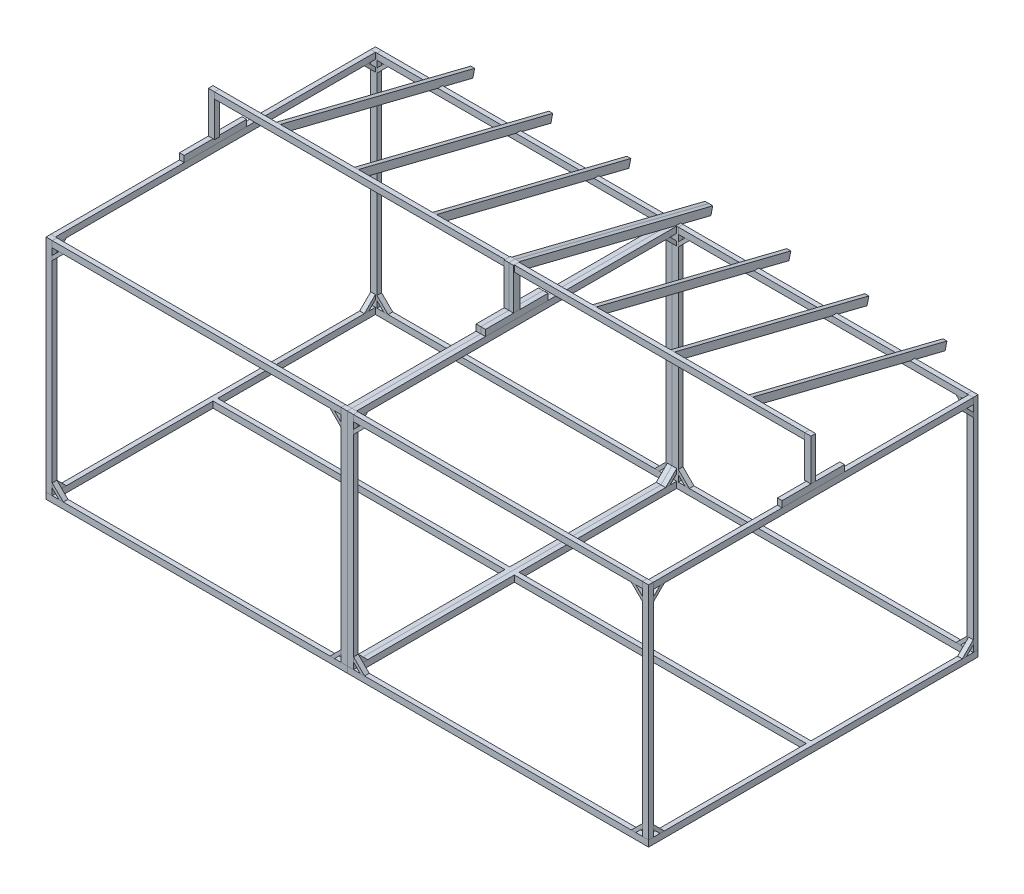
SolidWorks part; units mm, degrees
ref_plane "Front Plane" through (0, 0, 0) normal (0, 0, 1) x (1, 0, 0)
ref_plane "Top Plane" through (0, 0, 0) normal (0, 1, 0) x (1, 0, 0)
ref_plane "Right Plane" through (0, 0, 0) normal (1, 0, 0) x (0, 0, -1)
other "Configuration Table"
sketch "MetalBase" plane through (0, 0, 0) normal (0, 1, 0) x (1, 0, 0)
  line L0 (-60, -60) -> (7660, -60)
  line L1 (0, 0) -> (7600, 0)
  line L2 (0, 0) -> (0, 2020)
  line L3 (0, 4100) -> (7600, 4100)
  line L4 (7600, 0) -> (7600, 2020)
  line L5 (7660, -60) -> (7660, 4160)
  line L6 (-60, 4160) -> (7660, 4160)
  line L7 (-60, -60) -> (-60, 4160)
  line L8 (0, 2050) -> (7600, 2050) construction
  line L9 (0, 2020) -> (7600, 2020)
  line L10 (0, 2080) -> (7600, 2080)
  line L11 (0, 2080) -> (0, 4100)
  line L12 (7600, 2080) -> (7600, 4100)
  line L13 (0, 0) -> (0, 4100) construction
  line L15 (7600, 0) -> (7600, 4100) construction
  point P15 (7660, 2050)
  dimension "D1" = 4100
  dimension "D2" = 7600
  dimension "D6" = 4220
  dimension "D7" = 7720
  dimension "D3" = 60
  dimension "D4" = 30
  dimension "D5" = 30
sketch "InternalSpace" plane through (0, 0, 0) normal (0, 1, 0) x (1, 0, 0)
  line L26 (50, 50) -> (7550, 50)
  line L27 (7550, 50) -> (7550, 4050)
  line L28 (7550, 4050) -> (50, 4050)
  line L29 (50, 4050) -> (50, 50)
  line L30 (50, 50) -> (7550, 50)
  line L31 (7550, 50) -> (7550, 4050)
  line L32 (7550, 4050) -> (50, 4050)
  line L33 (50, 4050) -> (50, 50)
  dimension "D2" = 4000
  dimension "D3" = 7500
  dimension "D1" = 110
sketch "Furniture" plane through (0, 0, 0) normal (0, 1, 0) x (1, 0, 0)
  line L0 (6750, 2050) -> (6750, 4050)
  line L1 (2200, 2550) -> (1400, 2550)
  line L2 (2200, 2550) -> (2200, 4050)
  line L3 (2200, 4050) -> (1400, 4050)
  line L4 (1400, 2550) -> (1400, 4050)
  line L5 (1050, 50) -> (50, 50)
  line L6 (1050, 50) -> (1050, 2050)
  line L7 (1050, 2050) -> (50, 2050)
  line L8 (50, 50) -> (50, 2050)
  line L9 (6350, 2110) -> (7550, 2110)
  line L10 (2200, 4050) -> (2200, 150)
  line L11 (0, 0) -> (7600, 0) construction
  line L12 (6350, 50) -> (6350, 2110)
  line L13 (6470, 50) -> (6470, 1990)
  line L15 (2200, 2050) -> (7550, 2050) construction
  line L17 (1979.5569, 919.0285) -> (2200, 150)
  line L18 (6350, 150) -> (5722.0427, 459.305)
  line L19 (6710, 1120.0467) -> (7310, 1120.0467)
  line L24 (6710, 1120.0467) -> (6710, 1880.0467)
  line L25 (6710, 1880.0467) -> (7310, 1880.0467)
  line L26 (7310, 1120.0467) -> (7310, 1880.0467)
  line L27 (6350, 2110) -> (5750, 2110)
  line L28 (6350, 2110) -> (6350, 1510)
  line L29 (6350, 1510) -> (5750, 1510)
  line L30 (5750, 2110) -> (5750, 1510)
  line L31 (2320, 2050) -> (4320, 2050) construction
  line L32 (4320, 2050) -> (4320, 4050) construction
  line L33 (2200, 150) -> (2499.3532, 150) construction
  line L34 (2499.3532, 150) -> (2499.3532, 981.1813) construction
  line L35 (2499.3532, 981.1813) -> (2200, 981.1813) construction
  line L36 (2320, 4050) -> (2320, 150)
  line L37 (2200, 150) -> (2200, 50)
  line L38 (50, 50) -> (7550, 50) construction
  line L39 (2320, 150) -> (2320, 50)
  line L40 (7550, 4050) -> (50, 4050) construction
  line L41 (7550, 50) -> (7550, 4050) construction
  line L42 (50, 4050) -> (50, 50) construction
  line L43 (7550, 4050) -> (50, 4050) construction
  line L44 (7550, 50) -> (7550, 4050) construction
  line L45 (50, 50) -> (7550, 50) construction
  line L46 (50, 4050) -> (50, 50) construction
  line L47 (7010, 1120.0467) -> (7010, 1445.9123) construction
  line L48 (6470, 1990) -> (7550, 1990)
  line L49 (-60, -60) -> (-60, 4160) construction
  line L50 (7550, 809.8905) -> (7383.7397, 809.8905)
  line L51 (7550, 809.8905) -> (7550, 230.8186)
  line L52 (7550, 230.8186) -> (7383.7397, 230.8186)
  line L53 (7283.7397, 709.8905) -> (7283.7397, 330.8186)
  line L54 (7660, 4160) -> (-60, 4160) construction
  line L55 (-60, 4160) -> (-60, -60) construction
  line L56 (-60, -60) -> (7660, -60) construction
  line L57 (7660, -60) -> (7660, 4160) construction
  arc A1 (1979.5569, 919.0285) -> (1414.1883, 0) centre (2200, 150) ccw construction
  arc A2 (5722.0427, 459.305) -> (6350, 850) centre (6350, 150) cw construction
  arc A3 (7383.7397, 230.8186) -> (7283.7397, 330.8186) centre (7383.7397, 330.8186) cw
  arc A4 (7383.7397, 809.8905) -> (7283.7397, 709.8905) centre (7383.7397, 709.8905) ccw
  point P56 (7010, 1990)
  dimension "D13" = 600
  dimension "D21" = 100
  dimension "D1" = 1500
  dimension "D2" = 800
  dimension "D3" = 2000
  dimension "D4" = 1000
  dimension "D5" = 100
  dimension "D6" = 60
  dimension "D7" = 700
  dimension "D8" = 600
  dimension "D9" = 2260
  dimension "D10" = 800
  dimension "D11" = 100
  dimension "D12" = 760
  dimension "D14" = 2000
  dimension "D15" = 800
  dimension "D16" = 2000
  dimension "D17" = 600
  dimension "D18" = 60
  dimension "D19" = 4150
  dimension "D20" = 120
  dimension "D22" = 120
  dimension "D23" = 110
  dimension "D25" = 4220
  dimension "D26" = 1200
  dimension "D27" = 4030
  dimension "D24" = 110
sketch "Metal frame" plane through (0, 0, 0) normal (0, 1, 0) x (1, 0, 0)
  line L0 (0, 4100) -> (7600, 4100) construction
  line L1 (0, 4100) -> (7600, 4100)
  line L3 (0, 0) -> (0, 2020)
  line L4 (0, 0) -> (7600, 0) construction
  line L5 (0, 0) -> (7600, 0)
  line L7 (7600, 0) -> (7600, 2020)
  line L8 (-60, 4160) -> (7660, 4160)
  line L9 (7660, -60) -> (7660, 4160)
  line L10 (-60, -60) -> (7660, -60)
  line L11 (-60, -60) -> (-60, 4160)
  line L12 (0, 2050) -> (62.1159, 2050) construction
  line L13 (7600, 2080) -> (0, 2080)
  line L15 (7600, 2020) -> (0, 2020)
  line L17 (7600, 2080) -> (7600, 4100)
  line L18 (0, 2080) -> (0, 4100)
  line L19 (7600, 0) -> (7600, 4100) construction
  line L21 (0, 0) -> (0, 4100) construction
  point P14 (-60, 2050)
  dimension "D2" = 7720
  dimension "D3" = 4220
  dimension "D4" = 60
  dimension "D1" = 60
sketch "Walls bottom" plane through (0, 0, 0) normal (0, 1, 0) x (1, 0, 0)
  line L0 (-60, 4160) -> (7660, 4160) construction
  line L2 (-60, -60) -> (7660, -60) construction
  line L3 (7660, -60) -> (7660, 4160) construction
  line L4 (-60, -60) -> (-60, 4160) construction
  line L5 (-60, -60) -> (7660, -60)
  line L6 (7660, -60) -> (7660, 4160)
  line L7 (-60, 4160) -> (7660, 4160)
  line L8 (-60, -60) -> (-60, 4160)
  line L9 (40, 40) -> (40, 4060)
  line L10 (40, 4060) -> (7560, 4060)
  line L11 (7560, 40) -> (7560, 4060)
  line L12 (40, 40) -> (7560, 40)
  dimension "D2" = 4020
  dimension "D3" = 7520
  dimension "D4" = 7720
  dimension "D5" = 4220
  dimension "D1" = 100
sketch "Sketch15" plane through (0, 0, 0) normal (0, 1, 0) x (1, 0, 0)
  line L2 (7550, 50) -> (5502.4266, 50)
  line L3 (7550, 50) -> (7550, 1250)
  line L4 (7550, 1250) -> (5502.4266, 1250)
  line L5 (5502.4266, 50) -> (5502.4266, 1250)
  dimension "D1" = 1200
extrude "MetalFrame" add sketch "Metal frame" against normal blind 80 contours L11 L10 L9 L8 L15 L7 L5 L3 L13 L18 L1 L17 region at (3800, 0, -2050)
sketch "Sketch18" plane through (0, 0, 0) normal (0, 1, 0) x (1, 0, 0)
  line L0 (0, 0) -> (7600, 0) construction
  line L1 (3800, -1014.8769) -> (8467.9433, -1014.8769)
  line L2 (3800, -1014.8769) -> (3800, 5493.3133)
  line L3 (3800, 5493.3133) -> (8467.9433, 5493.3133)
  line L4 (8467.9433, -1014.8769) -> (8467.9433, 5493.3133)
  point P6 (3800, 0)
extrude "Cut-Extrude1" cut sketch "Sketch18" against normal through all
sketch "Sketch19" plane through (0, 0, 0) normal (0, 1, 0) x (1, 0, 0)
  line L0 (0, 0) -> (3800, 0) construction
  line L1 (3800, 4100) -> (3740, 4100)
  line L2 (3800, 4100) -> (3800, 0)
  line L3 (3800, 0) -> (3740, 0)
  line L4 (3740, 4100) -> (3740, 0)
  dimension "D1" = 60
extrude "Boss-Extrude1" add sketch "Sketch19" against normal blind 80
sketch "Roof" plane through (0, 0, 0) normal (1, 0, 0) x (0, 0, -1)
  line L0 (2050, 0) -> (2050, 3357.5) construction
  line L1 (4160, 0) -> (-60, 0) construction
  line L2 (4160, 0) -> (4160, 2830) construction
  line L3 (4160, 2830) -> (2050, 3357.5) construction
  line L4 (2050, 3357.5) -> (5424.8088, 3357.5) construction
  line L5 (4160, 2830) -> (4548.057, 2732.9857) construction
  line L6 (4160, 150) -> (-211.81, 150) construction
  line L7 (4160, 2830) -> (2960, 2830)
  line L8 (2960, 2830) -> (2960, 3130)
  line L9 (4160, 2750) -> (2401.0379, 2750) construction
  dimension "D2" = 1200
  dimension "D3" = 150
  dimension "D4" = 2174.9382
  dimension "D5" = 400
  dimension "D6" = 2574.9382
  dimension "D7" = 2830
  dimension "D8" = 300
  dimension "D9" = 3207.5
  dimension "D10" = 14.036
  dimension "D11" = 80
  dimension "D12" = 2600
sketch "Sketch23" plane through (-60, 0, 0) normal (1, 0, 0) x (0, 0, -1)
  line L0 (2050, 0) -> (2050, 3357.5) construction
  line L1 (4160, 0) -> (4100, 0)
  line L2 (4160, 0) -> (4160, 2830)
  line L3 (4160, 2830) -> (4100, 2830)
  line L4 (4100, 0) -> (4100, 2830)
  line L5 (0, 0) -> (0, 2830)
  line L6 (-60, 2830) -> (0, 2830)
  line L7 (-60, 0) -> (-60, 2830)
  line L8 (-60, 0) -> (0, 0)
  line L10 (0, 2830) -> (4100, 2830)
  line L11 (0, 2830) -> (0, 2750)
  line L12 (0, 2750) -> (4100, 2750)
  line L13 (4100, 2830) -> (4100, 2750)
  line M8 (-60, 0) -> (4160, 0)
  dimension "D1" = 60
  dimension "D2" = 80
extrude "Boss-Extrude5" add sketch "Sketch23" along normal blind 80 separate body contours L4 L3 L2 M8 | L7 L6 L5 M8 region at (-60, 1415, -4130) region at (-60, 1415, 30)
extrude "Boss-Extrude6" add sketch "Sketch23<3>" along normal blind 60 separate body contours L0 L12 L5 L10 | L12 L0 L10 L4 region at (-60, 2790, -1025) region at (-60, 2790, -3075)
sketch "Sketch23<3>" plane through (-60, 0, 0) normal (1, 0, 0) x (0, 0, -1) same geometry as "Sketch23"
extrude "Boss-Extrude7" add sketch "Sketch23<5>" against normal blind 80 from surface separate body contours L4 L3 L2 M8 | L7 L6 L5 M8 region at (-60, 1415, -4130) region at (-60, 1415, 30) starting at face at (3800, -40, -2050)
sketch "Sketch23<5>" plane through (-60, 0, 0) normal (1, 0, 0) x (0, 0, -1) same geometry as "Sketch23"
extrude "Boss-Extrude8" add sketch "Sketch23<6>" against normal blind 60 from surface separate body contours L12 L0 L10 L4 | L0 L12 L5 L10 region at (-60, 2790, -1025) region at (-60, 2790, -3075) starting at face at (3800, 1415, 30)
sketch "Sketch23<6>" plane through (-60, 0, 0) normal (1, 0, 0) x (0, 0, -1) same geometry as "Sketch23"
sketch "Sketch24" plane through (0, 2830, 0) normal (0, 1, 0) x (1, 0, 0)
  line L1 (20, 4160) -> (3720, 4160)
  line L2 (20, 4160) -> (20, 4100)
  line L3 (20, 4100) -> (3720, 4100)
  line L4 (3720, 4160) -> (3720, 4100)
  line L5 (20, 0) -> (3720, 0)
  line L6 (20, 0) -> (20, -60)
  line L7 (20, -60) -> (3720, -60)
  line L8 (3720, 0) -> (3720, -60)
extrude "Boss-Extrude9" add sketch "Sketch24" against normal blind 80 separate body
sketch "Sketch25" plane through (3800, 0, 0) normal (1, 0, 0) x (0, 0, -1)
  line L5 (2020, 2910) -> (2080, 2910)
  line L6 (2020, 2910) -> (2020, 3440)
  line L7 (2020, 3440) -> (2080, 3440)
  line L8 (2080, 2910) -> (2080, 3440)
  line L9 (2050, 0) -> (2050, 3357.5) construction
  line L10 (0, 2830) -> (4100, 2830) construction
  line L12 (1650, 2830) -> (2450, 2830)
  line L13 (1650, 2830) -> (1650, 2910)
  line L14 (1650, 2910) -> (2450, 2910)
  line L15 (2450, 2830) -> (2450, 2910)
  point P7 (2050, 3440)
  point P11 (2050, 2910)
  line M8 (4100, 2830) -> (0, 2830)
  dimension "D1" = 530
  dimension "D2" = 60
  dimension "D4" = 800
  dimension "D5" = 80
extrude "Boss-Extrude10" add sketch "Sketch25" along normal blind 80 from surface separate body contours L5 L8 L7 L6 region at (3800, 3175, -2050) starting at face at (-60, 2790, -2050)
extrude "Boss-Extrude13" add sketch "Sketch25<4>" against normal blind 60 from surface separate body contours L15 L14 L5 L13 M8 region at (3800, 2870, -2050) starting at face at (0, 2790, -2050)
sketch "Sketch25<4>" plane through (3800, 0, 0) normal (1, 0, 0) x (0, 0, -1) same geometry as "Sketch25"
extrude "Boss-Extrude20" add sketch "Sketch25<5>" against normal blind 60 separate body contours L15 L14 L5 L13 M8 region at (3800, 2870, -2050)
sketch "Sketch25<5>" plane through (3800, 0, 0) normal (1, 0, 0) x (0, 0, -1) same geometry as "Sketch25"
sketch "Sketch33" plane through (0, 2910, 0) normal (0, 1, 0) x (1, 0, 0)
  line L0 (3740, 1650) -> (3740, 2450) construction
  line L1 (3740, 2090) -> (3800, 2090)
  line L2 (3740, 2090) -> (3740, 2010)
  line L3 (3740, 2010) -> (3800, 2010)
  line L4 (3800, 2090) -> (3800, 2010)
  line L5 (3800, 1650) -> (3800, 2450) construction
  point P8 (3740, 2050)
  point P9 (3740, 2050)
  dimension "D1" = 80
extrude "Boss-Extrude21" add sketch "Sketch33" along normal up to surface (530 mm away) separate body up to face at (-20, 3440, -2050)
sketch "Sketch26" plane through (3800, 0, 0) normal (1, 0, 0) x (0, 0, -1)
  line L0 (4548.057, 2717.9857) -> (4160, 2815)
  line L1 (4548.057, 2717.9857) -> (4572.3106, 2815)
  line L3 (4572.3106, 2815) -> (2080, 3438.0776)
  line L4 (4100, 2815) -> (4100, 2830) construction
  line L5 (4100, 2830) -> (4160, 2830)
  line L6 (4160, 2830) -> (4160, 2815)
  line L7 (2080, 3335) -> (2080, 3438.0776)
  line L8 (4100, 2830) -> (2080, 3335)
  dimension "D1" = 100
extrude "Boss-Extrude12" add sketch "Sketch26" against normal blind 50 separate body
pattern_linear "LPattern1" count 4 spacing 1000 along (-1, 0, 0) of bodies 346
ref_plane "Plane1" through (1870, 0, 0) normal (-1, 0, 0) x (0, 0, 1)
sketch "Sketch27" plane through (3740, 0, 0) normal (-1, 0, 0) x (0, 0, 1)
  line L0 (-2020, 2910) -> (-2020, 3440) construction
  line L1 (-2080, 3440) -> (-2020, 3440)
  line L2 (-2080, 3440) -> (-2080, 3360)
  line L3 (-2080, 3360) -> (-2020, 3360)
  line L4 (-2020, 3440) -> (-2020, 3360)
  line L5 (-2050, 0) -> (-2050, 3357.5) construction
  point P4 (-2050, 3440)
  dimension "D1" = 80
  dimension "D2" = 60
extrude "Boss-Extrude22" add sketch "Sketch27" along normal up to surface (3720 mm away) separate body up to face at (20, 3175, -2050)
mirror "Mirror2" about plane through (3800, -80, 1014.8769) normal (-1, 0, 0) of bodies 336 338 340 342 335 337 339 341 330 412 411 349 348 347 346 410 350 351 354 352 353
sketch "Sketch28" plane through (0, 0, 60) normal (0, 0, 1) x (1, 0, 0)
  line L0 (20, 2665.1472) -> (104.8528, 2750)
  line L1 (20, 2750) -> (3720, 2750) construction
  line L2 (20, 0) -> (20, 2830) construction
  line L3 (20, 2608.5786) -> (161.4214, 2750)
  line L4 (20, 2665.1472) -> (20, 2750) construction
  line L5 (20, 2750) -> (104.8528, 2750) construction
  line L6 (3720, 2750) -> (20, 0) construction
  line L7 (20, 2750) -> (3720, 0) construction
  line L8 (104.8528, 2750) -> (161.4214, 2750)
  line L9 (20, 2665.1472) -> (20, 2608.5786)
  line L10 (1870, 1375) -> (1870, 2476.0047) construction
  line L11 (1870, 1375) -> (689.8346, 1375) construction
  line L12 (20, 0) -> (104.8528, 0) construction
  line L13 (20, 84.8528) -> (20, 0) construction
  line L14 (20, 84.8528) -> (20, 141.4214)
  line L15 (104.8528, 0) -> (161.4214, 0)
  line L16 (20, 141.4214) -> (161.4214, 0)
  line L17 (20, 84.8528) -> (104.8528, 0)
  line L18 (3720, 84.8528) -> (3720, 0) construction
  line L19 (3720, 0) -> (3635.1472, 0) construction
  line L20 (3720, 2750) -> (3635.1472, 2750) construction
  line L21 (3720, 2665.1472) -> (3720, 2750) construction
  line L22 (3720, 84.8528) -> (3635.1472, 0)
  line L23 (3720, 141.4214) -> (3578.5786, 0)
  line L24 (3635.1472, 0) -> (3578.5786, 0)
  line L25 (3720, 84.8528) -> (3720, 141.4214)
  line L26 (3720, 2665.1472) -> (3720, 2608.5786)
  line L27 (3635.1472, 2750) -> (3578.5786, 2750)
  line L28 (3720, 2608.5786) -> (3578.5786, 2750)
  line L29 (3720, 2665.1472) -> (3635.1472, 2750)
  line L30 (3800, -80) -> (3800, -237.922) construction
  line L31 (3880, 2665.1472) -> (3880, 2750) construction
  line L32 (3880, 2750) -> (3964.8528, 2750) construction
  line L33 (3880, 0) -> (3964.8528, 0) construction
  line L34 (3880, 84.8528) -> (3880, 0) construction
  line L35 (7580, 84.8528) -> (7580, 0) construction
  line L36 (7580, 0) -> (7495.1472, 0) construction
  line L37 (5730, 1375) -> (6910.1654, 1375) construction
  line L38 (5730, 1375) -> (5730, 2476.0047) construction
  line L39 (7580, 2750) -> (3880, 0) construction
  line L40 (3880, 2750) -> (7580, 0) construction
  line L41 (7580, 2750) -> (7495.1472, 2750) construction
  line L42 (7580, 2665.1472) -> (7580, 2750) construction
  line L43 (3880, 2665.1472) -> (3964.8528, 2750)
  line L44 (3880, 2608.5786) -> (4021.4214, 2750)
  line L45 (3964.8528, 2750) -> (4021.4214, 2750)
  line L46 (3880, 2665.1472) -> (3880, 2608.5786)
  line L47 (3880, 84.8528) -> (3880, 141.4214)
  line L48 (3964.8528, 0) -> (4021.4214, 0)
  line L49 (3880, 141.4214) -> (4021.4214, 0)
  line L50 (3880, 84.8528) -> (3964.8528, 0)
  line L51 (7580, 84.8528) -> (7495.1472, 0)
  line L52 (7580, 141.4214) -> (7438.5786, 0)
  line L53 (7495.1472, 0) -> (7438.5786, 0)
  line L54 (7580, 84.8528) -> (7580, 141.4214)
  line L55 (7580, 2665.1472) -> (7580, 2608.5786)
  line L56 (7495.1472, 2750) -> (7438.5786, 2750)
  line L57 (7580, 2608.5786) -> (7438.5786, 2750)
  line L58 (7580, 2665.1472) -> (7495.1472, 2750)
  point P14 (1870, 1375)
  point P58 (5730, 1375)
  dimension "D1" = 40
  dimension "D2" = 200
extrude "Boss-Extrude15" add sketch "Sketch28" against normal blind 60 separate body
ref_plane "Plane2" through (0, 0, -2050) normal (0, 0, 1) x (1, 0, 0)
mirror "Mirror5" about plane through (0, 0, -2050) normal (0, 0, 1) of bodies 379 382 378 377 380 381 384 383
sketch "Sketch29" plane through (-60, 0, 0) normal (-1, 0, 0) x (0, 0, 1)
  line L0 (-141.4214, 2750) -> (0, 2608.5786)
  line L1 (0, 2750) -> (-4100, 2750) construction
  line L2 (0, 0) -> (0, 2830) construction
  line L3 (0, 2608.5786) -> (0, 2665.1472)
  line L4 (0, 2665.1472) -> (-84.8528, 2750)
  line L5 (-84.8528, 2750) -> (-141.4214, 2750)
  line L6 (-141.4214, 2750) -> (0, 2750) construction
  line L7 (0, 2750) -> (0, 2608.5786) construction
  line L8 (-4100, 2750) -> (0, 0) construction
  line L9 (0, 2750) -> (-4100, 0) construction
  line L10 (-2050, 1375) -> (-2050, 2472.0101) construction
  line L11 (-2050, 0) -> (-2050, 3357.5) construction
  line L12 (-2050, 1375) -> (-3378.9698, 1375) construction
  line L13 (-4100, 2750) -> (-4100, 2608.5786) construction
  line L14 (-3958.5786, 2750) -> (-4100, 2750) construction
  line L15 (-4015.1472, 2750) -> (-3958.5786, 2750)
  line L16 (-4100, 2665.1472) -> (-4015.1472, 2750)
  line L17 (-4100, 2608.5786) -> (-4100, 2665.1472)
  line L18 (-3958.5786, 2750) -> (-4100, 2608.5786)
  line L19 (-3958.5786, 0) -> (-4100, 0) construction
  line L20 (-4100, 0) -> (-4100, 141.4214) construction
  line L21 (0, 0) -> (0, 141.4214) construction
  line L22 (-141.4214, 0) -> (0, 0) construction
  line L23 (-3958.5786, 0) -> (-4100, 141.4214)
  line L24 (-4100, 141.4214) -> (-4100, 84.8528)
  line L25 (-4100, 84.8528) -> (-4015.1472, 0)
  line L26 (-4015.1472, 0) -> (-3958.5786, 0)
  line L27 (-84.8528, 0) -> (-141.4214, 0)
  line L28 (0, 84.8528) -> (-84.8528, 0)
  line L29 (0, 141.4214) -> (0, 84.8528)
  line L30 (-141.4214, 0) -> (0, 141.4214)
  dimension "D1" = 200
  dimension "D2" = 40
extrude "Boss-Extrude16" add sketch "Sketch29" against normal blind 60 separate body
extrude "Boss-Extrude17" add sketch "Sketch29<2>" against normal blind 60 from surface separate body starting at face at (3740, 2790, -2050)
sketch "Sketch29<2>" plane through (-60, 0, 0) normal (-1, 0, 0) x (0, 0, 1) same geometry as "Sketch29"
extrude "Boss-Extrude18" add sketch "Sketch29<4>" against normal blind 60 from surface separate body starting at face at (3800, 2790, -2050)
sketch "Sketch29<4>" plane through (-60, 0, 0) normal (-1, 0, 0) x (0, 0, 1) same geometry as "Sketch29"
extrude "Boss-Extrude19" add sketch "Sketch29<5>" against normal blind 60 from surface separate body starting at face at (7600, 2790, -2050)
sketch "Sketch29<5>" plane through (-60, 0, 0) normal (-1, 0, 0) x (0, 0, 1) same geometry as "Sketch29"
